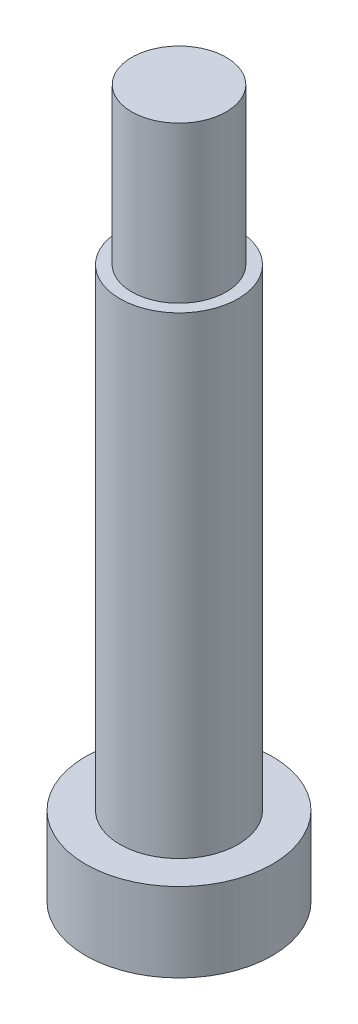
SolidWorks part; units mm, degrees
ref_plane "前视基准面" through (0, 0, 0) normal (0, 0, 1) x (1, 0, 0)
ref_plane "上视基准面" through (0, 0, 0) normal (0, 1, 0) x (1, 0, 0)
ref_plane "右视基准面" through (0, 0, 0) normal (1, 0, 0) x (0, 0, -1)
other "Configuration Table"
sketch "草图1" plane through (0, 0, 0) normal (0, 1, 0) x (1, 0, 0)
  circle A0 centre (0, 0) radius 5
  circle A1 centre (0, 0) radius 7.9
  circle A2 centre (0, 0) radius 4
  dimension "D1" = 8
  dimension "D2" = 10
  dimension "D3" = 15.8
extrude "凸台-拉伸1" add sketch "草图1" along normal blind 59.9 contours A2 region at (0, 0, 0)
extrude "凸台-拉伸2" add sketch "草图1<3>" along normal blind 46.7 contours A0 A2 region at (-4.8586, 0, 0)
sketch "草图1<3>" plane through (0, 0, 0) normal (0, 1, 0) x (1, 0, 0) same geometry as "草图1"
extrude "凸台-拉伸3" add sketch "草图1<4>" along normal blind 6.7 contours A1 A0 region at (-7.6766, 0, 0)
sketch "草图1<4>" plane through (0, 0, 0) normal (0, 1, 0) x (1, 0, 0) same geometry as "草图1"
sketch "草图2" plane through (0, 0, 0) normal (0, -1, 0) x (1, 0, 0)
  line L1 (2.5, 1.4434) -> (0, 2.8868)
  line L2 (0, 2.8868) -> (-2.5, 1.4434)
  line L3 (-2.5, 1.4434) -> (-2.5, -1.4434)
  line L4 (-2.5, -1.4434) -> (0, -2.8868)
  line L5 (0, -2.8868) -> (2.5, -1.4434)
  line L6 (2.5, -1.4434) -> (2.5, 1.4434)
  circle A0 centre (0, 0) radius 2.5 construction
  dimension "D1" = 5
extrude "切除-拉伸1" cut sketch "草图2" against normal blind 3
